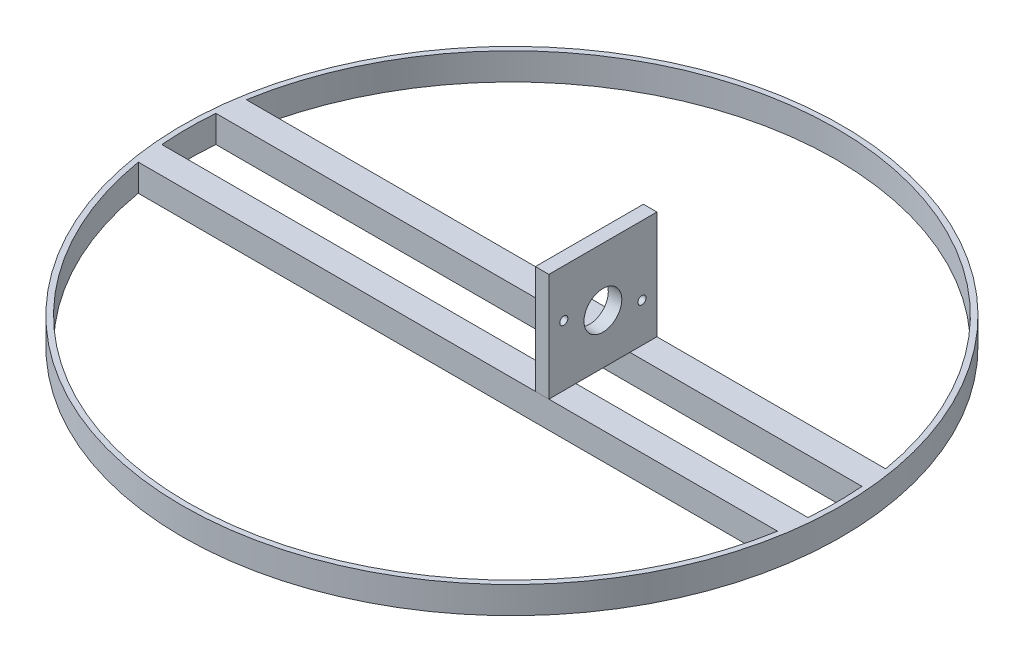
SolidWorks part; units mm, degrees
ref_plane "Front Plane" through (0, 0, 0) normal (0, 0, 1) x (1, 0, 0)
ref_plane "Top Plane" through (0, 0, 0) normal (0, 1, 0) x (1, 0, 0)
ref_plane "Right Plane" through (0, 0, 0) normal (1, 0, 0) x (0, 0, -1)
sketch "Sketch1" plane through (0, 0, 0) normal (0, 1, 0) x (1, 0, 0)
  circle A0 centre (-133.6717, -100.8607) radius 122
  circle A1 centre (-133.6717, -100.8607) radius 120
  dimension "D1" = 244
  dimension "D2" = 2
extrude "Boss-Extrude1" add sketch "Sketch1" along normal blind 10
sketch "Sketch2" plane through (0, 0, 0) normal (1, 0, 0) x (0, 0, -1)
  line L0 (-100.8607, 10) -> (-100.8607, -30.5393) construction
  line L1 (21.1393, 10) -> (-222.8607, 10) construction
  line L2 (-222.8607, 0) -> (21.1393, 0) construction
  line L3 (-120.8607, 10) -> (-110.8607, 10)
  line L4 (-120.8607, 10) -> (-120.8607, 0)
  line L5 (-120.8607, 0) -> (-110.8607, 0)
  line L6 (-110.8607, 10) -> (-110.8607, 0)
  line L8 (-90.8607, 10) -> (-90.8607, 0)
  line L9 (-80.8607, 0) -> (-90.8607, 0)
  line L10 (-80.8607, 10) -> (-80.8607, 0)
  line L11 (-80.8607, 10) -> (-90.8607, 10)
  dimension "D1" = 10
extrude "Boss-Extrude2" add sketch "Sketch2" against normal blind 300
sketch "Sketch3" plane through (0, 0, 0) normal (0, 1, 0) x (1, 0, 0)
  line L0 (-133.6717, -90.8607) -> (-133.6717, -110.8607) construction
  line L1 (-253.2543, -90.8607) -> (-14.0891, -90.8607) construction
  line L2 (-253.2543, -110.8607) -> (-14.0891, -110.8607) construction
  circle A0 centre (-133.6717, -100.8607) radius 122
extrude "Cut-Extrude5" cut sketch "Sketch3" against normal through all and the other way through all flip side to cut contours A0
sketch "Sketch4" plane through (0, 0, 0) normal (1, 0, 0) x (0, 0, -1)
  line L0 (21.1393, 10) -> (-222.8607, 10) construction
  line L1 (-120.8607, 10) -> (-80.8607, 10)
  line L2 (-120.8607, 10) -> (-120.8607, 50)
  line L3 (-120.8607, 50) -> (-80.8607, 50)
  line L4 (-80.8607, 50) -> (-80.8607, 10)
  line L5 (-120.8607, 10) -> (-220.8607, 10) construction
  line L7 (-100.8607, 50) -> (-100.8607, 10) construction
  line L8 (-100.8607, 30) -> (-80.8607, 30) construction
  circle A0 centre (-86.3892, 24.5198) radius 1.5
  circle A1 centre (-115.3323, 32.4125) radius 1.5
  circle A2 centre (-100.8607, 28.4662) radius 7
  dimension "D3" = 14
  dimension "D1" = 40
  dimension "D2" = 40
extrude "Boss-Extrude3" add sketch "Sketch4" along normal blind 5 from offset 105 separate body offset against normal yes
sketch "Sketch6" plane through (0, 0, 0) normal (0, 1, 0) x (1, 0, 0)
  line L0 (-133.6717, -80.8607) -> (-133.6717, -120.8607) construction
  line L1 (-251.9933, -80.8607) -> (-15.3501, -80.8607) construction
  line L2 (-251.9933, -120.8607) -> (-15.3501, -120.8607) construction
  circle A0 centre (-133.6717, -100.8607) radius 10
  circle A1 centre (-133.6717, -100.8607) radius 20
